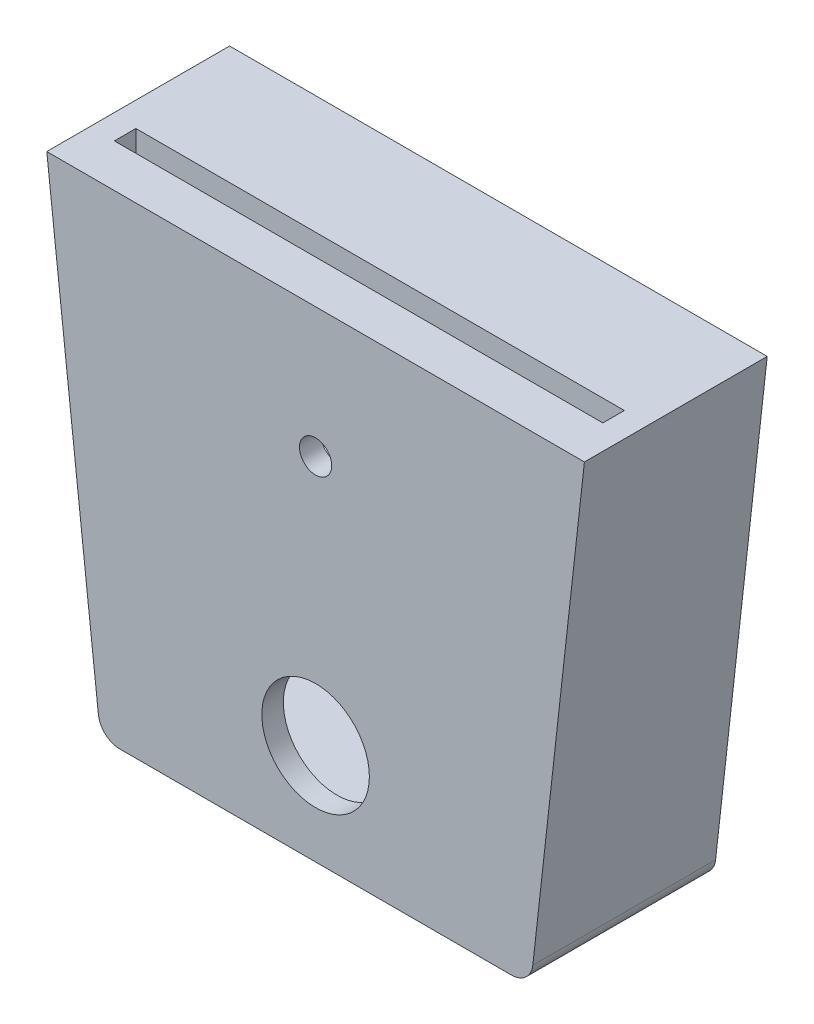
SolidWorks part; units mm, degrees
ref_plane "Front Plane" through (0, 0, 0) normal (0, 0, 1) x (1, 0, 0)
ref_plane "Top Plane" through (0, 0, 0) normal (0, 1, 0) x (1, 0, 0)
ref_plane "Right Plane" through (0, 0, 0) normal (1, 0, 0) x (0, 0, -1)
sketch "Sketch1" plane through (0, 0, 0) normal (0, 0, 1) x (1, 0, 0)
  line L0 (0, 56.7961) -> (0, -56.7961) construction
  line L1 (63.5, 56.7961) -> (-63.5, 56.7961)
  line L2 (-63.5, 56.7961) -> (-51.3049, -52.2806)
  line L3 (-46.2563, -56.7961) -> (46.2563, -56.7961)
  line L4 (63.5, 56.7961) -> (51.3049, -52.2806)
  arc A0 (-51.3049, -52.2806) -> (-46.2563, -56.7961) centre (-46.2563, -51.7161) ccw
  arc A1 (51.3049, -52.2806) -> (46.2563, -56.7961) centre (46.2563, -51.7161) cw
  circle A2 centre (0, 26.1693) radius 3.81
  circle A3 centre (0, -32.9791) radius 12.7
  point P10 (-50.8, -56.7961)
  point P16 (0, -32.9791)
  dimension "D4" = 5.08
  dimension "D6" = 7.62
  dimension "D7" = 25.4
  dimension "D8" = 30.6268
  dimension "D9" = 23.8171
  dimension "D1" = 50.8
  dimension "D2" = 63.5
  dimension "D3" = 56.7961
  dimension "D5" = 109.0767
extrude "Boss-Extrude1" add sketch "Sketch1" against normal blind 5.08
sketch "Sketch2" plane through (0, 0, -5.08) normal (0, 0, 1) x (1, 0, 0)
  line L0 (0, 56.7961) -> (0, -56.7961) construction
  line L1 (63.5, 56.7961) -> (-63.5, 56.7961)
  line L2 (-63.5, 56.7961) -> (-51.3049, -52.2806)
  line L3 (-46.2563, -56.7961) -> (46.2563, -56.7961)
  line L4 (63.5, 56.7961) -> (51.3049, -52.2806)
  line L5 (-46.2563, -56.7961) -> (46.2563, -56.7961) construction
  line L6 (-57.6928, 50.5747) -> (57.6928, 50.5747)
  line L7 (57.6928, 50.5747) -> (46.7612, -47.2006)
  line L8 (41.7126, -51.7161) -> (-41.7126, -51.7161)
  line L9 (-57.6928, 50.5747) -> (-46.7612, -47.2006)
  arc A0 (-51.3049, -52.2806) -> (-46.2563, -56.7961) centre (-46.2563, -51.7161) ccw
  arc A1 (51.3049, -52.2806) -> (46.2563, -56.7961) centre (46.2563, -51.7161) cw
  circle A2 centre (0, 26.1693) radius 3.81
  circle A3 centre (0, -32.9791) radius 12.7
  arc A4 (46.7612, -47.2006) -> (41.7126, -51.7161) centre (41.7126, -46.6361) cw
  arc A5 (-46.7612, -47.2006) -> (-41.7126, -51.7161) centre (-41.7126, -46.6361) ccw
  point P10 (-50.8, -56.7961)
  point P27 (0, -51.7161)
  point P28 (0, 50.5747)
  arc M12 (51.3049, -52.2806) -> (46.2563, -56.7961) centre (46.2563, -51.7161) cw
  line M13 (46.2563, -56.7961) -> (-46.2563, -56.7961)
  arc M14 (-46.2563, -56.7961) -> (-51.3049, -52.2806) centre (-46.2563, -51.7161) cw
  line M15 (-51.3049, -52.2806) -> (-63.5, 56.7961)
  line M16 (-63.5, 56.7961) -> (63.5, 56.7961)
  line M17 (63.5, 56.7961) -> (51.3049, -52.2806)
  dimension "D4" = 5.08
  dimension "D6" = 7.62
  dimension "D7" = 25.4
  dimension "D8" = 30.6268
  dimension "D9" = 23.8171
  dimension "D11" = 5.08
  dimension "D1" = 50.8
  dimension "D2" = 63.5
  dimension "D3" = 6.2214
  dimension "D5" = 109.0767
  dimension "D10" = 0
extrude "Boss-Extrude2" add sketch "Sketch2" against normal blind 38.1 contours L0 L1 L8 A4 L7 L6 M17 M12 M13 | L0 L6 L9 A5 L8 L3 M16 M14 M15 region at (31.75, 55.4948, -5.08) region at (-1.3014, 53.6854, -5.08)
sketch "Sketch3" plane through (0, 56.7961, 0) normal (0, 1, 0) x (1, 0, 0)
  line L0 (57.6928, 10.16) -> (57.6928, 15.24)
  line L1 (57.6928, 10.16) -> (-57.6928, 10.16)
  line L2 (57.6928, 15.24) -> (-57.6928, 15.24)
  line L3 (-57.6928, 10.16) -> (-57.6928, 15.24)
  line L6 (63.5, 0) -> (-63.5, 0) construction
  line L8 (-63.5, 43.18) -> (-63.5, 0) construction
  dimension "D1" = 115.3856
  dimension "D2" = 5.8072
  dimension "D3" = 10.16
  dimension "D4" = 5.08
extrude "Cut-Extrude2" cut sketch "Sketch3" against normal blind 6.35
sketch "Sketch4" plane through (0, 0, -43.18) normal (0, 0, -1) x (-1, 0, 0)
  line L0 (0, 50.5747) -> (0, -51.7161) construction
  line L1 (57.6928, 50.5747) -> (-57.6928, 50.5747) construction
  line L2 (-41.7126, -51.7161) -> (41.7126, -51.7161) construction
  line L3 (-52.9958, 8.564) -> (-33.9458, 8.564)
  line L4 (-57.6928, 50.5747) -> (-46.7612, -47.2006) construction
  line L5 (-33.9458, 8.564) -> (-33.9458, -4.136)
  line L6 (-33.9458, -4.136) -> (-51.5759, -4.136)
  line L7 (-57.6928, 50.5747) -> (-46.7612, -47.2006) construction
  line L8 (33.9458, -4.136) -> (51.5759, -4.136)
  line L9 (33.9458, 8.564) -> (33.9458, -4.136)
  line L10 (52.9958, 8.564) -> (33.9458, 8.564)
  line L11 (-51.5759, -4.136) -> (-52.9958, 8.564)
  line L12 (52.9958, 8.564) -> (51.5759, -4.136)
  dimension "D1" = 19.05
  dimension "D2" = 12.7
  dimension "D3" = 33.9458
extrude "Boss-Extrude3" add sketch "Sketch4" against normal blind 2.54
sketch "Sketch5" plane through (0, 0, -43.18) normal (0, 0, -1) x (-1, 0, 0)
  line L0 (-43.4708, 8.564) -> (-42.7609, -4.136) construction
  line L1 (-33.9458, 8.564) -> (-52.9958, 8.564) construction
  line L2 (-51.5759, -4.136) -> (-33.9458, -4.136) construction
  line L3 (0, 50.5747) -> (0, -51.7161) construction
  line L4 (57.6928, 50.5747) -> (-57.6928, 50.5747) construction
  line L5 (-41.7126, -51.7161) -> (41.7126, -51.7161) construction
  circle A0 centre (-43.1159, 2.214) radius 1.905
  circle A1 centre (43.1159, 2.214) radius 1.905
  dimension "D1" = 3.81
extrude "Cut-Extrude3" cut sketch "Sketch5" against normal blind 2.54
